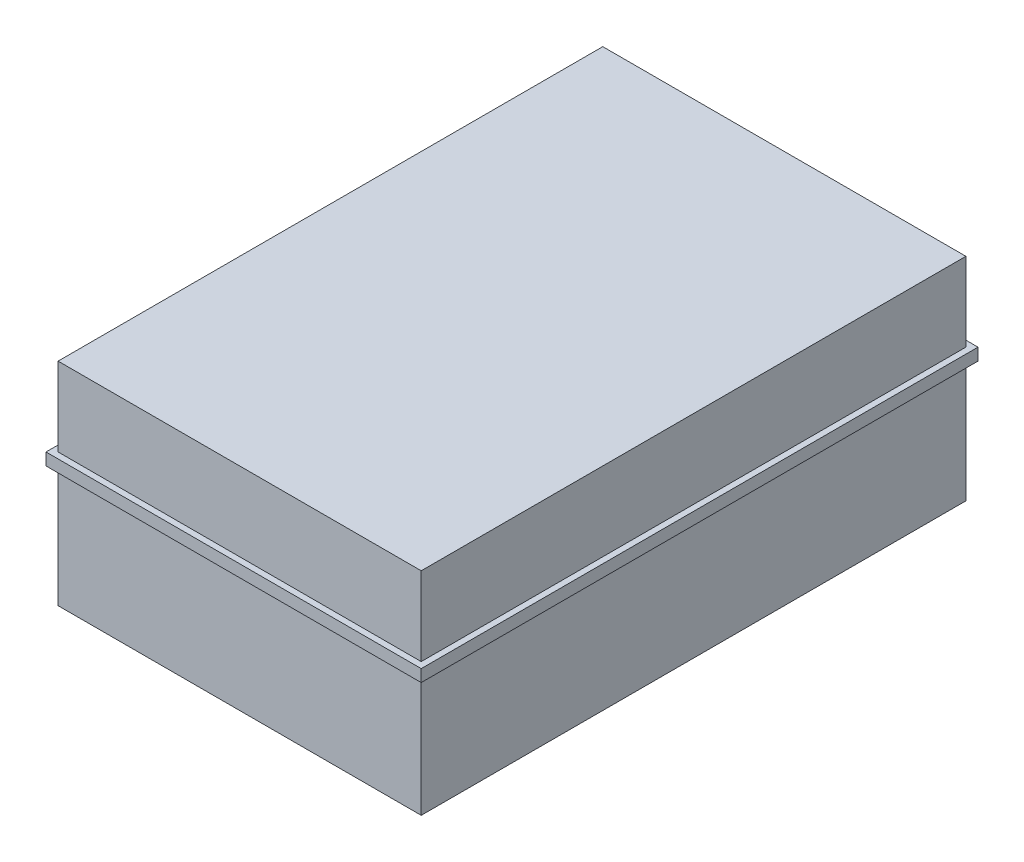
SolidWorks part; units mm, degrees
material "1023 Carbon Steel Sheet (SS)"
ref_plane "Front Plane" through (0, 0, 0) normal (0, 0, 1) x (1, 0, 0)
ref_plane "Top Plane" through (0, 0, 0) normal (0, 1, 0) x (1, 0, 0)
ref_plane "Right Plane" through (0, 0, 0) normal (1, 0, 0) x (0, 0, -1)
sketch "Sketch1" plane through (0, 0, 0) normal (0, 1, 0) x (1, 0, 0)
  line L0 (62, 91.5977) -> (-62, 91.5977)
  line L1 (60, 89.5977) -> (-60, 89.5977)
  line L2 (60, 89.5977) -> (60, -90.4023)
  line L3 (60, -90.4023) -> (-60, -90.4023)
  line L4 (-60, 89.5977) -> (-60, -90.4023)
  line L5 (60, 89.5977) -> (-60, -90.4023) construction
  line L6 (60, -90.4023) -> (-60, 89.5977) construction
  line L7 (-62, 91.5977) -> (-62, -92.4023)
  line L8 (62, -92.4023) -> (-62, -92.4023)
  line L9 (62, 91.5977) -> (62, -92.4023)
  point P1 (0, -0.4023)
  dimension "D1" = 2
extrude "Boss-Extrude1" add sketch "Sketch1" along normal blind 4 contours L9 L0 L7 L8 L4 L1 L2 L3 region at (61.7781, 0, 0.4023)
extrude "Boss-Extrude2" add sketch "Sketch1<3>" along normal blind 30 and the other way blind 40 contours L1 L4 L3 L2 region at (0, 0, 0.4023)
sketch "Sketch1<3>" plane through (0, 0, 0) normal (0, 1, 0) x (1, 0, 0) same geometry as "Sketch1"
